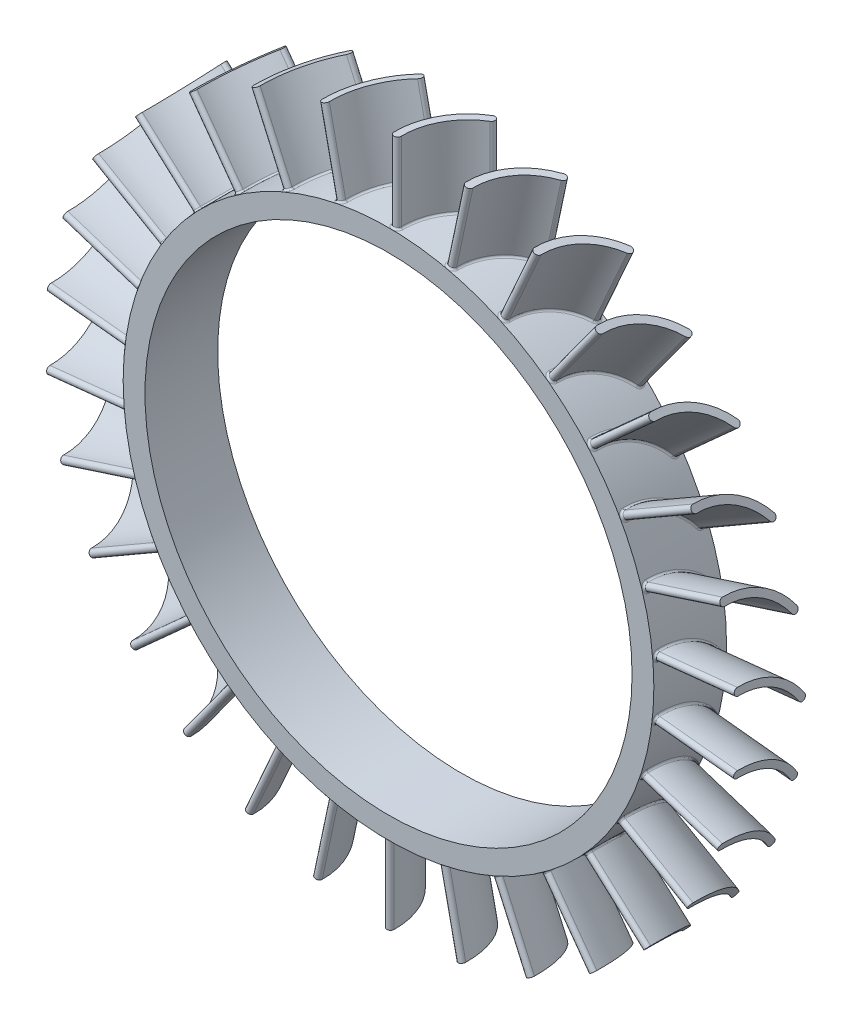
SolidWorks part; units mm, degrees
ref_plane "Front Plane" through (0, 0, 0) normal (0, 0, 1) x (1, 0, 0)
ref_plane "Top Plane" through (0, 0, 0) normal (0, 1, 0) x (1, 0, 0)
ref_plane "Right Plane" through (0, 0, 0) normal (1, 0, 0) x (0, 0, -1)
sketch "Sketch1" plane through (0, 0, 0) normal (0, 0, 1) x (1, 0, 0)
  circle A0 centre (0, 0) radius 73
  circle A1 centre (0, 0) radius 67
  dimension "D1" = 134
  dimension "D2" = 146
extrude "Boss-Extrude1" add sketch "Sketch1" along normal mid plane 20
sketch "Sketch2" plane through (0, 0, 0) normal (0, 1, 0) x (1, 0, 0)
  line L0 (-73, -10) -> (73, -10) construction
  line L1 (67, 10) -> (-67, 10) construction
  arc A0 (-0.0154, -8.5) -> (9.6648, 9) centre (19.9812, -8.1339) cw
  arc A1 (1.9843, -8.4634) -> (10.6964, 7.2866) centre (19.9812, -8.1339) cw
  arc A3 (-0.0154, -8.5) -> (1.9843, -8.4634) centre (0.9844, -8.4817) ccw
  arc A4 (9.6648, 9) -> (10.6964, 7.2866) centre (10.1806, 8.1433) cw
  dimension "D3" = 20
  dimension "D1" = 1.5
  dimension "D2" = 1
  dimension "D4" = 2
extrude "Boss-Extrude2" add sketch "Sketch2" along normal blind 27 from offset 68
fillet "Fillet1" radius 0.5 4 edges at (0.8792, 72.9947, 9.4761) (1.2928, 72.9886, 1.0105) (9.2833, 72.4073, -7.7018) (2.4685, 72.9583, 3.9741)
pattern_circular "CirPattern1" count 30 over 360 about axis through (0, 0, 10) along (0, 0, -1) of "Boss-Extrude2", "Fillet1"
